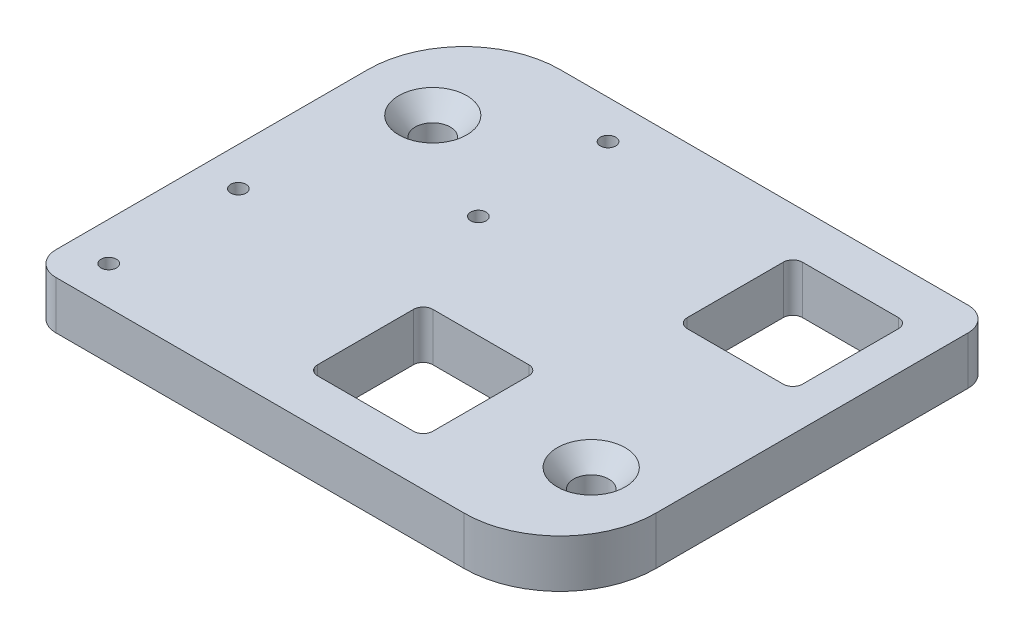
SolidWorks part; units mm, degrees
ref_plane "Top" through (0, 0, 0) normal (0, 0, 1) x (1, 0, 0)
ref_plane "Front" through (0, 0, 0) normal (0, 1, 0) x (1, 0, 0)
ref_plane "Right" through (0, 0, 0) normal (1, 0, 0) x (0, 0, -1)
sketch "Base Sketch" plane through (0, 0, 0) normal (0, 1, 0) x (1, 0, 0)
  line L1 (-27.5, 45) -> (27.5, 45)
  line L2 (-27.5, 45) -> (-27.5, 0)
  line L3 (-27.5, 0) -> (27.5, 0)
  line L4 (27.5, 45) -> (27.5, 0)
  dimension "D1" = 55
  dimension "D2" = 45
extrude "Base Extrude" add sketch "Base Sketch" against normal blind 5
hole_wizard "Mosfet Mounting Holes" positions "Mosfet Mounting Holes Position Sketch" profile "Mosfet Mounting Holes Profile Sketch" hole size "M2x0.4" standard "ANSI Metric" end condition through all
sketch "Mosfet Mounting Holes Position Sketch" plane through (0, 0, 0) normal (0, 1, 0) x (1, 0, 0)
  line L0 (-23.5, 17.5) -> (-23.5, 4) construction
  line L2 (-8.5, 41) -> (-8.5, 27.5) construction
  line L4 (-27.5, 45) -> (-27.5, 0) construction
  line L5 (-27.5, 0) -> (27.5, 0) construction
  line L6 (27.5, 45) -> (-27.5, 45) construction
  line L7 (27.5, 0) -> (27.5, 45) construction
  point P0 (-23.5, 4)
  point P2 (-23.5, 17.5)
  point P4 (-8.5, 27.5)
  point P6 (-8.5, 41)
  dimension "D1" = 13.5
  dimension "D2" = 36
sketch "Mosfet Mounting Holes Profile Sketch" plane through (-23.5, 0, -4) normal (1, 0, 0) x (0, 0, 1)
  line L0 (0, 0) -> (0, 5)
  line L1 (0, 5) -> (0.8, 5)
  line L2 (0.8, 5) -> (0.8, 0)
  line L5 (0.8, 0) -> (0, 0)
  line L11 (0, -6.35) -> (0, 107.95) construction
  dimension "Thru Hole Dia." = 1.6
  dimension "Thru Hole Depth" = 5
hole_wizard "Mounting Holes" positions "Mounting Holes Position Sketch" profile "Mounting Hole Profile Sketch" countersink size "#6" standard "ANSI Inch" end condition through all
sketch "Mounting Holes Position Sketch" plane through (0, 0, 0) normal (0, 1, 0) x (1, 0, 0)
  line L0 (-27.5, 34.25) -> (-8.5, 34.25) construction
  line L2 (-8.5, 41) -> (-8.5, 27.5) construction
  line L3 (-23.5, 10.75) -> (27.5, 10.75) construction
  line L5 (-23.5, 17.5) -> (-23.5, 4) construction
  line L7 (-27.5, 45) -> (-27.5, 0) construction
  line L8 (27.5, 0) -> (27.5, 45) construction
  point P0 (-20, 34.25)
  point P2 (20, 10.75)
sketch "Mounting Hole Profile Sketch" plane through (-20, 0, -34.25) normal (1, 0, 0) x (0, 0, 1)
  line L0 (0, 0) -> (0, 5)
  line L1 (0, 5) -> (1.8288, 5)
  line L2 (1.8288, 5) -> (1.8288, 1.9723)
  line L3 (1.8288, 1.9723) -> (3.5433, 0)
  line L5 (3.5433, 0) -> (0, 0)
  line L6 (-1.8288, 1.9723) -> (-3.5433, 0) construction
  line L11 (0, -6.35) -> (0, 107.95) construction
  dimension "Thru Hole Dia." = 3.6576
  dimension "Thru Hole Depth" = 5
  dimension "Near C'Sink Dia." = 7.0866
  dimension "Near C'Sink Angle" = 82
sketch "Pin Relief Sketch" plane through (0, 0, 0) normal (0, 1, 0) x (1, 0, 0)
  line L0 (-23.5, 17.5) -> (-23.5, 4) construction
  line L1 (-3.5, 16.75) -> (8.5, 16.75)
  line L2 (-3.5, 16.75) -> (-3.5, 4.75)
  line L3 (-3.5, 4.75) -> (8.5, 4.75)
  line L4 (8.5, 16.75) -> (8.5, 4.75)
  line L5 (-23.5, 10.75) -> (-3.5, 10.75) construction
  line L6 (-8.5, 34.25) -> (11.5, 34.25) construction
  line L7 (-8.5, 41) -> (-8.5, 27.5) construction
  line L8 (11.5, 40.25) -> (23.5, 40.25)
  line L9 (11.5, 40.25) -> (11.5, 28.25)
  line L10 (11.5, 28.25) -> (23.5, 28.25)
  line L11 (23.5, 40.25) -> (23.5, 28.25)
  dimension "D1" = 12
  dimension "D2" = 20
  dimension "D3" = 12
extrude "Cut-Extrude1" cut sketch "Pin Relief Sketch" against normal through all
fillet "Fillet1" radius 10 2 edges at (-27.5, -2.5, -45) (27.5, -2.5, 0)
fillet "Fillet2" radius 2.5 2 edges at (-27.5, -2.5, 0) (27.5, -2.5, -45)
fillet "Fillet3" radius 1 8 edges at (8.5, -2.5, -16.75) (-3.5, -2.5, -16.75) (-3.5, -2.5, -4.75) (8.5, -2.5, -4.75) (23.5, -2.5, -28.25) (11.5, -2.5, -28.25) (11.5, -2.5, -40.25) (23.5, -2.5, -40.25)
